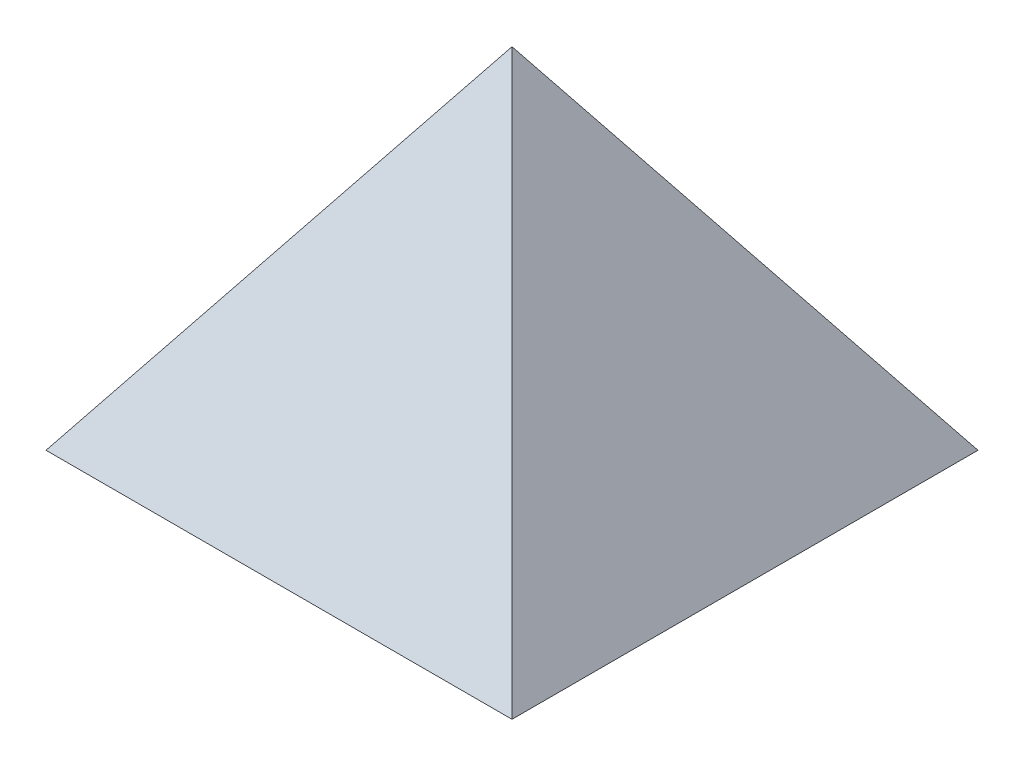
SolidWorks part; units mm, degrees
ref_plane "Front Plane" through (0, 0, 0) normal (0, 0, 1) x (1, 0, 0)
ref_plane "Top Plane" through (0, 0, 0) normal (0, 1, 0) x (1, 0, 0)
ref_plane "Right Plane" through (0, 0, 0) normal (1, 0, 0) x (0, 0, -1)
sketch "Sketch3" plane through (0, 0, 0) normal (0, 1, 0) x (1, 0, 0)
  line L1 (-50.8, -50.8) -> (50.8, -50.8)
  line L2 (-50.8, -50.8) -> (-50.8, 50.8)
  line L3 (-50.8, 50.8) -> (50.8, 50.8)
  line L4 (50.8, -50.8) -> (50.8, 50.8)
  line L5 (-50.8, -50.8) -> (50.8, 50.8) construction
  line L6 (-50.8, 50.8) -> (50.8, -50.8) construction
  point P0 (0, 0)
  dimension "D1" = 101.6
  dimension "D2" = 101.6
ref_plane "Plane4" through (0, 76.2, 0) normal (0, 1, 0) x (1, 0, 0)
sketch "Sketch4" plane through (0, 76.2, 0) normal (0, 1, 0) x (1, 0, 0)
  point P0 (0, 0)
loft "Loft1" add profiles "Sketch4", "Sketch3"
sketch "Sketch7" plane through (0, 23.4462, -35.1692) normal (0, 0.5547, -0.8321) x (-1, 0, 0)
  line L0 (-31.3891, -16.7488) -> (31.3891, -16.7488) construction
  line L1 (31.3891, -16.7488) -> (0, 39.8387) construction
  line L2 (0, 39.8387) -> (-31.3891, -16.7488) construction
  line L3 (0, 63.4022) -> (-50.8, -28.1788) construction
  line L4 (0, 63.4022) -> (50.8, -28.1788) construction
  line L5 (-50.8, -28.1788) -> (50.8, -28.1788) construction
  text T0 "R" font "Century Gothic" height in points 60
  text T1 "9" font "Century Gothic" height in points 60
  text T2 "&" font "Century Gothic" height in points 60
  text T3 "#" font "Century Gothic" height in points 60
  point P21 (0, 0)
  dimension "D1" = 11.43
  dimension "D2" = 11.43
  dimension "D3" = 11.43
  dimension "D4" = 22.86
  dimension "D5" = 6.35
  dimension "D6" = 0
  dimension "D7" = 17.78
  dimension "D8" = 0
  dimension "D9" = 4.318
  dimension "D10" = 3.81
  dimension "D11" = 7.62
shell "Shell2" thickness 2.54 removed face at (0, 0, 0)
sketch "Sketch8" plane through (0, 0, 0) normal (0, -1, 0) x (1, 0, 0)
  line L1 (47.7473, -47.7473) -> (-47.7473, -47.7473)
  line L2 (47.7473, -47.7473) -> (47.7473, 47.7473)
  line L3 (47.7473, 47.7473) -> (-47.7473, 47.7473)
  line L4 (-47.7473, -47.7473) -> (-47.7473, 47.7473)
extrude "Boss-Extrude1" add sketch "Sketch8" against normal blind 2.54
sketch "Sketch9" plane through (0, 23.4462, -35.1692) normal (0, 0.5547, -0.8321) x (-1, 0, 0)
  line L0 (-50.8, -28.1788) -> (50.8, -28.1788) construction
  circle A0 centre (35.4584, -19.2888) radius 5.715
  dimension "D1" = 11.43
  dimension "D2" = 8.89
  dimension "D3" = 15.3416
extrude "Cut-Extrude1" cut sketch "Sketch9" against normal blind 2.54
extrude "Boss-Extrude2" [suppressed] add sketch "Sketch7" along normal blind 2.54 and the other way blind 2.54
sketch "Sketch10" plane through (0, 23.4462, -35.1692) normal (0, 0.5547, -0.8321) x (-1, 0, 0)
  line L3 (0, 63.4022) -> (-50.8, -28.1788)
  line L4 (-50.8, -28.1788) -> (50.8, -28.1788)
  line L5 (50.8, -28.1788) -> (0, 63.4022)
  line L6 (0, 63.4022) -> (-50.8, -28.1788)
  line L7 (-50.8, -28.1788) -> (50.8, -28.1788)
  line L8 (50.8, -28.1788) -> (0, 63.4022)
  dimension "D1" = 0
extrude "Cut-Extrude2" [suppressed] cut sketch "Sketch10" against normal through all draft 20 draft outward yes
sketch "Sketch15" plane through (-35.1692, 23.4462, 0) normal (-0.8321, 0.5547, 0) x (0, 0, 1)
  line L0 (-31.3891, -16.7488) -> (31.3891, -16.7488) construction
  line L1 (31.3891, -16.7488) -> (0, 39.8387) construction
  line L2 (0, 39.8387) -> (-31.3891, -16.7488) construction
  line L4 (-50.8, -28.1788) -> (50.8, -28.1788) construction
  line L5 (0, 63.4022) -> (50.8, -28.1788) construction
  line L6 (0, 63.4022) -> (-50.8, -28.1788) construction
  text T0 "O" font "Century Gothic" height in points 60
  text T1 "#" font "Century Gothic" height in points 60
  text T2 "9" font "Century Gothic" height in points 60
  text T3 "&" font "Century Gothic" height in points 60
  point P14 (0, 0)
  dimension "D1" = 11.43
  dimension "D2" = 11.43
  dimension "D3" = 11.43
  dimension "D4" = 21.59
  dimension "D5" = 8.382
  dimension "D6" = 23.622
  dimension "D7" = 0
  dimension "D8" = 4.064
  dimension "D9" = 6.096
  dimension "D10" = 3.048
extrude "Boss-Extrude3" [suppressed] add sketch "Sketch15" along normal blind 2.54 and the other way blind 2.54
sketch "Sketch16" plane through (0, 23.4462, 35.1692) normal (0, 0.5547, 0.8321) x (1, 0, 0)
  line L6 (0, 39.8387) -> (-31.3891, -16.7488)
  line L7 (-31.3891, -16.7488) -> (31.3891, -16.7488)
  line L8 (31.3891, -16.7488) -> (0, 39.8387)
  line L9 (0, 39.8387) -> (-31.3891, -16.7488) construction
  line L10 (-31.3891, -16.7488) -> (31.3891, -16.7488) construction
  line L11 (31.3891, -16.7488) -> (0, 39.8387) construction
  text T0 "S" font "Century Gothic" height in points 60
  text T1 "&" font "Century Gothic" height in points 60
  text T2 "#" font "Century Gothic" height in points 60
  text T3 "9" font "Century Gothic" height in points 60
  dimension "D1" = 11.43
extrude "Boss-Extrude4" [suppressed] add sketch "Sketch16" along normal blind 2.54 and the other way blind 2.54
sketch "Sketch17" plane through (35.1692, 23.4462, 0) normal (0.8321, 0.5547, 0) x (0, 0, -1)
  line L6 (0, 39.8387) -> (-31.3891, -16.7488)
  line L7 (-31.3891, -16.7488) -> (31.3891, -16.7488)
  line L8 (31.3891, -16.7488) -> (0, 39.8387)
  line L9 (0, 39.8387) -> (-31.3891, -16.7488) construction
  line L10 (-31.3891, -16.7488) -> (31.3891, -16.7488) construction
  line L11 (31.3891, -16.7488) -> (0, 39.8387) construction
  text T0 "E" font "Century Gothic" height in points 60
  text T1 "&" font "Century Gothic" height in points 60
  text T2 "#" font "Century Gothic" height in points 60
  text T3 "9" font "Century Gothic" height in points 60
  dimension "D1" = 11.43
extrude "Boss-Extrude5" [suppressed] add sketch "Sketch17" along normal blind 2.54 and the other way blind 2.54
sketch "Sketch20" [suppressed] plane through (0, 23.4462, -35.1692) normal (0, 0.5547, -0.8321) x (-1, 0, 0)
  line L0 (-15.1966, -12.4684) -> (-16.7867, -10.8465) construction
  line L1 (-16.7867, -10.8465) -> (-19.1781, -8.3343) construction
  line L2 (-15.292, -14.3192) -> (-12.907, -16.7488) construction
  line L3 (-12.907, -16.7488) -> (-10.9925, -16.7488) construction
  line L4 (-12.3027, -11.8896) -> (-13.2027, -10.8465) construction
  line L5 (17.6796, -17.1558) -> (22.5674, -10.007) construction
  line L6 (20.9551, -9.9116) -> (16.5411, -16.364) construction
  line L7 (16.5411, -16.364) -> (17.6796, -17.1558) construction
  line L8 (5.8127, 2.7028) -> (2.9315, 2.7028) construction
  line L9 (2.9315, 2.7028) -> (3.4785, 6.3663) construction
  line L10 (3.4785, 6.3663) -> (6.2197, 6.3663) construction
  line L11 (6.2197, 6.3663) -> (6.2197, 7.3839) construction
  line L12 (6.2197, 7.3839) -> (3.6312, 7.3839) construction
  line L13 (3.6312, 7.3839) -> (4.3944, 12.4721) construction
  line L14 (4.3944, 12.4721) -> (3.1669, 12.4721) construction
  line L15 (3.1669, 12.4721) -> (2.4036, 7.3839) construction
  line L16 (2.4036, 7.3839) -> (-0.8464, 7.3839) construction
  line L17 (-0.8464, 7.3839) -> (-0.0832, 12.4721) construction
  line L18 (-0.0832, 12.4721) -> (-1.3107, 12.4721) construction
  line L19 (-1.3107, 12.4721) -> (-2.0739, 7.3839) construction
  line L20 (-2.0739, 7.3839) -> (-5.1777, 7.3839) construction
  line L21 (-5.1777, 7.3839) -> (-5.1777, 6.3663) construction
  line L22 (-5.1777, 6.3663) -> (-2.2266, 6.3663) construction
  line L23 (-2.2266, 6.3663) -> (-2.7767, 2.7028) construction
  line L24 (-2.7767, 2.7028) -> (-5.5847, 2.7028) construction
  line L25 (-5.5847, 2.7028) -> (-5.5847, 1.6852) construction
  line L26 (-5.5847, 1.6852) -> (-2.9294, 1.6852) construction
  line L27 (-2.9294, 1.6852) -> (-3.753, -3.81) construction
  line L28 (-3.753, -3.81) -> (-2.5223, -3.81) construction
  line L29 (-2.5223, -3.81) -> (-1.6987, 1.6852) construction
  line L30 (-1.6987, 1.6852) -> (1.5482, 1.6852) construction
  line L31 (1.5482, 1.6852) -> (0.7246, -3.81) construction
  line L32 (0.7246, -3.81) -> (1.9552, -3.81) construction
  line L33 (1.9552, -3.81) -> (2.7789, 1.6852) construction
  line L34 (2.7789, 1.6852) -> (5.8127, 1.6852) construction
  line L35 (5.8127, 1.6852) -> (5.8127, 2.7028) construction
  line L36 (-4.3147, 32.8537) -> (-4.3147, 16.9787) construction
  line L37 (-4.3147, 16.9787) -> (-2.8901, 16.9787) construction
  line L38 (-2.8901, 16.9787) -> (-2.8901, 24.3056) construction
  line L39 (-2.8901, 24.3056) -> (-1.7325, 24.3056) construction
  line L40 (-1.7325, 24.3056) -> (4.0998, 16.9787) construction
  line L41 (4.0998, 16.9787) -> (5.8615, 16.9787) construction
  line L42 (5.8615, 16.9787) -> (0.0293, 24.3056) construction
  line L43 (-1.1378, 32.8537) -> (-4.3147, 32.8537) construction
  line L44 (-15.1966, -12.4684) -> (-16.7867, -10.8465)
  line L45 (-16.7867, -10.8465) -> (-19.1781, -8.3343)
  line L46 (-15.292, -14.3192) -> (-12.907, -16.7488)
  line L47 (-12.907, -16.7488) -> (-10.9925, -16.7488)
  line L48 (-12.3027, -11.8896) -> (-13.2027, -10.8465)
  line L49 (17.6796, -17.1558) -> (22.5674, -10.007)
  line L50 (20.9551, -9.9116) -> (16.5411, -16.364)
  line L51 (16.5411, -16.364) -> (17.6796, -17.1558)
  line L52 (5.8127, 2.7028) -> (2.9315, 2.7028)
  line L53 (2.9315, 2.7028) -> (3.4785, 6.3663)
  line L54 (3.4785, 6.3663) -> (6.2197, 6.3663)
  line L55 (6.2197, 6.3663) -> (6.2197, 7.3839)
  line L56 (6.2197, 7.3839) -> (3.6312, 7.3839)
  line L57 (3.6312, 7.3839) -> (4.3944, 12.4721)
  line L58 (4.3944, 12.4721) -> (3.1669, 12.4721)
  line L59 (3.1669, 12.4721) -> (2.4036, 7.3839)
  line L60 (2.4036, 7.3839) -> (-0.8464, 7.3839)
  line L61 (-0.8464, 7.3839) -> (-0.0832, 12.4721)
  line L62 (-0.0832, 12.4721) -> (-1.3107, 12.4721)
  line L63 (-1.3107, 12.4721) -> (-2.0739, 7.3839)
  line L64 (-2.0739, 7.3839) -> (-5.1777, 7.3839)
  line L65 (-5.1777, 7.3839) -> (-5.1777, 6.3663)
  line L66 (-5.1777, 6.3663) -> (-2.2266, 6.3663)
  line L67 (-2.2266, 6.3663) -> (-2.7767, 2.7028)
  line L68 (-2.7767, 2.7028) -> (-5.5847, 2.7028)
  line L69 (-5.5847, 2.7028) -> (-5.5847, 1.6852)
  line L70 (-5.5847, 1.6852) -> (-2.9294, 1.6852)
  line L71 (-2.9294, 1.6852) -> (-3.753, -3.81)
  line L72 (-3.753, -3.81) -> (-2.5223, -3.81)
  line L73 (-2.5223, -3.81) -> (-1.6987, 1.6852)
  line L74 (-1.6987, 1.6852) -> (1.5482, 1.6852)
  line L75 (1.5482, 1.6852) -> (0.7246, -3.81)
  line L76 (0.7246, -3.81) -> (1.9552, -3.81)
  line L77 (1.9552, -3.81) -> (2.7789, 1.6852)
  line L78 (2.7789, 1.6852) -> (5.8127, 1.6852)
  line L79 (5.8127, 1.6852) -> (5.8127, 2.7028)
  line L80 (-4.3147, 32.8537) -> (-4.3147, 16.9787)
  line L81 (-4.3147, 16.9787) -> (-2.8901, 16.9787)
  line L82 (-2.8901, 16.9787) -> (-2.8901, 24.3056)
  line L83 (-2.8901, 24.3056) -> (-1.7325, 24.3056)
  line L84 (-1.7325, 24.3056) -> (4.0998, 16.9787)
  line L85 (4.0998, 16.9787) -> (5.8615, 16.9787)
  line L86 (5.8615, 16.9787) -> (0.0293, 24.3056)
  line L87 (-1.1378, 32.8537) -> (-4.3147, 32.8537)
  line L88 (-16.262, -13.3334) -> (-18.8092, -10.7352) construction
  line L89 (-1.546, 2.7028) -> (1.7008, 2.7028) construction
  line L90 (1.7008, 2.7028) -> (2.251, 6.3663) construction
  line L91 (2.251, 6.3663) -> (-0.9991, 6.3663) construction
  line L92 (-0.9991, 6.3663) -> (-1.546, 2.7028) construction
  line L93 (0.0865, 31.2255) -> (-2.8901, 31.2255) construction
  line L94 (-2.8901, 31.2255) -> (-2.8901, 25.9338) construction
  line L95 (-2.8901, 25.9338) -> (0.0165, 25.9116) construction
  line L96 (-16.262, -13.3334) -> (-18.8092, -10.7352)
  line L97 (-1.546, 2.7028) -> (1.7008, 2.7028)
  line L98 (1.7008, 2.7028) -> (2.251, 6.3663)
  line L99 (2.251, 6.3663) -> (-0.9991, 6.3663)
  line L100 (-0.9991, 6.3663) -> (-1.546, 2.7028)
  line L101 (0.0865, 31.2255) -> (-2.8901, 31.2255)
  line L102 (-2.8901, 31.2255) -> (-2.8901, 25.9338)
  line L103 (-2.8901, 25.9338) -> (0.0165, 25.9116)
  spline S0 degree 3 poles (-1211.016, 1589.987) (37.766, 13.4921) (7.6344, 6.2742) (-14.1134, -11.5897) (-53.1946, -43.2278) (-85.728, -82.5813) (-1389.1326, 1438.1841) knots -32.138305 -32.138305 -32.138305 -32.138305 0.211979 0.448506 0.7115 58.901746 58.901746 58.901746 58.901746 only from (-13.2027, -10.8465) to (-15.1966, -12.4684) construction
  spline S1 degree 3 poles (1213.8222, -1582.7079) (-59.2714, -14.9852) (-32.1987, -19.4765) (-18.3945, -7.68) (-18.0524, -7.3699) (-17.7457, -7.0763) (-17.4726, -6.7989) (-17.2383, -6.5365) (-17.0382, -6.2896) (-16.823, -5.988) (-16.6097, -5.6247) (-16.4256, -5.1931) (-14.3902, 1.855) (-54.3612, 14.9464) (1965.0086, -276.0147) knots -10.451764 -10.451764 -10.451764 -10.451764 0.105642 0.203981 0.294597 0.378912 0.455227 0.524996 0.587023 0.643258 0.744199 0.835566 0.920643 5.054796 5.054796 5.054796 5.054796 only from (-19.1781, -8.3343) to (-16.2842, -4.3623) construction
  spline S2 degree 3 poles (1973.7793, 194.0657) (-51.4849, -21.917) (-14.7602, -10.7247) (-16.381, -3.6302) (-16.5173, -3.2786) (-16.7047, -2.9408) (-16.9387, -2.6211) (-17.2268, -2.3363) (-17.559, -2.0826) (-17.9391, -1.8731) (-18.3484, -1.6979) (-18.7863, -1.5731) (-28.3709, -0.0333) (-40.7081, -35.3731) (109.6458, 1994.1865) knots -4.132886 -4.132886 -4.132886 -4.132886 0.074197 0.148047 0.222587 0.300557 0.37994 0.460256 0.543595 0.630739 0.720813 0.811094 0.904147 6.547345 6.547345 6.547345 6.547345 only from (-16.2842, -4.3623) to (-19.7187, -1.4843) construction
  spline S3 degree 3 poles (-96.2047, 1996.9105) (-1.1162, -30.4751) (-11.5215, -0.5018) (-20.4569, -1.5327) (-20.8041, -1.6037) (-21.1379, -1.6965) (-21.4523, -1.828) (-21.7571, -1.974) (-28.7123, -6.4707) (-17.3542, -34.8268) (-1252.8823, 1574.128) knots -9.254206 -9.254206 -9.254206 -9.254206 0.135626 0.266321 0.392983 0.516276 0.637901 0.758631 0.879017 9.511566 9.511566 9.511566 9.511566 only from (-19.7187, -1.4843) to (-22.3041, -2.3684) construction
  spline S4 degree 3 poles (-1373.4615, 1472.0964) (6.456, -12.0068) (-17.6213, 2.8205) (-22.7023, -2.7663) (-22.8532, -2.9916) (-22.984, -3.225) (-23.0817, -3.4736) (-23.1511, -3.734) (-24.2565, -10.0188) (7.5119, -18.9958) (-2017.4492, 146.1379) knots -9.92722 -9.92722 -9.92722 -9.92722 0.131449 0.257906 0.381113 0.501946 0.623787 0.745627 0.870676 9.333997 9.333997 9.333997 9.333997 only from (-22.3041, -2.3684) to (-23.2041, -4.286) construction
  spline S5 degree 3 poles (-2015.3815, -179.3604) (8.1381, 12.7979) (-24.523, 2.2958) (-23.123, -4.9748) (-23.0129, -5.329) (-22.8872, -5.632) (-22.7505, -5.8874) (-22.6249, -6.1097) (-22.4672, -6.3547) (-22.2813, -6.6244) (-22.0732, -6.9226) (-21.8364, -7.2447) (-11.1832, -21.2383) (14.4163, -23.4182) (-1566.5908, -1277.2192) knots -4.999634 -4.999634 -4.999634 -4.999634 0.080148 0.163016 0.250603 0.343925 0.395896 0.456723 0.525583 0.60322 0.689875 0.784341 0.887706 13.206881 13.206881 13.206881 13.206881 only from (-23.2041, -4.286) to (-21.2865, -7.9526) construction
  spline S6 degree 3 poles (-1258.508, 1562.9871) (24.2351, -1.632) (-7.0336, 4.4872) (-22.3165, -8.8237) (-22.7641, -9.2371) (-23.1684, -9.6273) (-23.5183, -10.0028) (-23.829, -10.351) (-24.0821, -10.6865) (-24.3605, -11.0941) (-24.6251, -11.6) (-24.8626, -12.2056) (-27.2311, -22.2702) (15.6235, -37.4436) (-2014.3666, 191.7077) knots -8.568615 -8.568615 -8.568615 -8.568615 0.10298 0.198866 0.287721 0.369301 0.444358 0.512001 0.573159 0.6279 0.727593 0.821895 0.911698 5.220728 5.220728 5.220728 5.220728 only from (-21.2865, -7.9526) to (-25.0358, -13.4256) construction
  spline S7 degree 3 poles (-2021.6065, -128.263) (6.2867, 5.1239) (-26.1824, -5.6484) (-24.9748, -14.1887) (-24.8934, -14.5482) (-24.7742, -14.8912) (-24.6218, -15.2182) (-24.4366, -15.5285) (-24.217, -15.8206) (-23.9682, -16.0957) (-23.6901, -16.345) (-23.3888, -16.5651) (-23.0626, -16.7449) (-22.7168, -16.8957) (-22.3495, -17.0143) (-21.9592, -17.095) (-12.5827, -18.3074) (-1.1632, 14.4463) (-121.9288, -2014.4951) knots -4.067076 -4.067076 -4.067076 -4.067076 0.064496 0.126884 0.187124 0.246441 0.305977 0.36519 0.424708 0.486277 0.548235 0.609019 0.670238 0.731947 0.79524 0.860594 0.928698 5.460162 5.460162 5.460162 5.460162 only from (-25.0358, -13.4256) to (-21.1211, -17.1558) construction
  spline S8 degree 3 poles (105.4375, -2012.9623) (-46.4777, 21.2594) (-31.562, -18.9943) (-19.8205, -17.028) (-19.1948, -16.8473) (-18.6812, -16.6419) (-18.2652, -16.4305) (-17.923, -16.2343) (-17.554, -16.0024) (-17.1543, -15.7376) (-16.7283, -15.4348) (-16.2759, -15.0935) (-0.8159, -3.2749) (-0.512, 27.4826) (1265.8678, -1549.7318) knots -5.076743 -5.076743 -5.076743 -5.076743 0.099479 0.19723 0.295054 0.393883 0.447109 0.506216 0.572397 0.644405 0.723232 0.808942 0.900994 9.532577 9.532577 9.532577 9.532577 only from (-21.1211, -17.1558) to (-15.292, -14.3192) construction
  spline S9 degree 3 poles (1466.2951, 1330.8092) (10.7971, -58.9757) (4.6752, -32.6363) (-11.6795, -16.046) (-46.1587, 19.0578) (-86.0822, 48.5893) (1308.3834, 1484.0297) knots -33.089565 -33.089565 -33.089565 -33.089565 0.227433 0.471173 0.72797 71.654968 71.654968 71.654968 71.654968 only from (-10.9925, -16.7488) to (-12.4395, -15.2732) construction
  spline S10 degree 3 poles (1478.6723, 1316.367) (21.6085, -71.1392) (9.5912, -37.4776) (-13.3896, -14.3089) (-33.2104, 6.0641) (-62.8373, 16.5022) (1352.8811, 1445.4489) knots -37.612235 -37.612235 -37.612235 -37.612235 0.277779 0.537034 0.77778 33.71632 33.71632 33.71632 33.71632 only from (-12.4395, -15.2732) to (-14.2267, -13.4542) construction
  spline S11 degree 3 poles (-1341.9172, 1481.3358) (-50.1448, -60.2796) (-36.1748, -31.1825) (-13.2966, -12.6979) (27.3008, 20.3634) (73.138, 46.6573) (-1148.1149, 1631.7199) knots -34.846163 -34.846163 -34.846163 -34.846163 0.235134 0.479473 0.735631 63.573763 63.573763 63.573763 63.573763 only from (-14.2267, -13.4542) to (-12.3027, -11.8896) construction
  spline S12 degree 3 poles (1668.2044, -1146.2833) (-10.7043, -24.0989) (14.6997, -22.3807) (23.0413, -9.2835) (23.2502, -8.9385) (23.4351, -8.6061) (23.6071, -8.2897) (23.7545, -7.9854) (23.8874, -7.6962) (24.0286, -7.3301) (24.1749, -6.8869) (24.3038, -6.3632) (25.8363, 4.0048) (-8.4285, 16.8712) (2020.7141, -124.8402) knots -8.910329 -8.910329 -8.910329 -8.910329 0.087946 0.171747 0.250583 0.32591 0.396143 0.462994 0.525418 0.583838 0.694397 0.800583 0.90168 6.863836 6.863836 6.863836 6.863836 only from (22.5674, -10.007) to (24.3959, -5.345) construction
  spline S13 degree 3 poles (2017.2359, 161.6488) (-15.7997, -30.0858) (26.4308, -14.9769) (24.2462, -4.0769) (24.0418, -3.4701) (23.7584, -2.8888) (23.4055, -2.3477) (22.9865, -1.8624) (22.5022, -1.4445) (21.9636, -1.0938) (21.3819, -0.814) (20.7699, -0.6115) (9.3934, 1.527) (-5.7744, -39.9197) (169.9675, 1993.6962) knots -4.058346 -4.058346 -4.058346 -4.058346 0.083474 0.165402 0.248081 0.332 0.416297 0.498735 0.580591 0.664318 0.748057 0.830997 0.914468 5.233291 5.233291 5.233291 5.233291 only from (24.3959, -5.345) to (19.4763, -0.4667) construction
  spline S14 degree 3 poles (-127.7649, 1993.9185) (44.9609, -40.2134) (29.6793, 1.5495) (18.1496, -0.6145) (17.5161, -0.8243) (16.9113, -1.1088) (16.3516, -1.4626) (15.8504, -1.8742) (15.419, -2.3441) (15.0601, -2.8658) (14.7751, -3.4318) (14.5708, -4.034) (12.3869, -15.2278) (54.9701, -30.4623) (-1979.29, 151.7815) knots -4.230904 -4.230904 -4.230904 -4.230904 0.086062 0.17094 0.255778 0.341735 0.427007 0.509416 0.590092 0.671171 0.751825 0.832673 0.914751 5.113135 5.113135 5.113135 5.113135 only from (19.4763, -0.4667) to (14.4232, -5.3291) construction
  spline S15 degree 3 poles (-1982.2681, -117.5572) (47.9002, 15.9969) (13.054, 3.6541) (14.5041, -6.2813) (14.6155, -6.7306) (14.7685, -7.1623) (14.9702, -7.5716) (15.213, -7.9642) (15.5053, -8.3323) (15.8332, -8.6801) (16.1939, -8.9969) (16.5785, -9.2736) (16.9829, -9.5088) (17.4066, -9.6985) (17.8487, -9.8511) (18.3108, -9.9534) (28.6348, -11.379) (41.3764, 22.9838) (-94.5785, -2006.6302) knots -3.797348 -3.797348 -3.797348 -3.797348 0.064609 0.12725 0.188534 0.248578 0.309139 0.369772 0.431966 0.495825 0.559795 0.622662 0.68409 0.74564 0.807138 0.869869 0.933705 4.947275 4.947275 4.947275 4.947275 only from (14.4232, -5.3291) to (19.2855, -10.0324) construction
  spline S16 degree 3 poles (119.0292, -2007.3224) (-12.2834, 26.9885) (23.1112, -49.516) (47.1443, 32.0919) (208.2591, -2000.898) knots -26.084625 -26.084625 -26.084625 -26.084625 0.492142 27.359519 27.359519 27.359519 27.359519 only from (19.2855, -10.0324) to (20.9551, -9.9116) construction
  spline S17 degree 3 poles (13.5867, -1975.4638) (-27.7179, 48.4127) (-13.0892, 23.5705) (0.9903, 24.337) (1.4338, 24.3781) (1.85, 24.4341) (2.2379, 24.5083) (2.5993, 24.5911) (2.9306, 24.6983) (3.3329, 24.8507) (3.7885, 25.0886) (4.2778, 25.4317) (4.6965, 25.8417) (5.045, 26.3085) (5.3186, 26.8263) (5.5171, 27.385) (7.6544, 37.9462) (-35.3403, 52.6149) (1999.1094, -131.0337) knots -5.078847 -5.078847 -5.078847 -5.078847 0.062052 0.120621 0.175789 0.228041 0.2771 0.323011 0.366127 0.406783 0.483311 0.556994 0.62881 0.700809 0.773286 0.846279 0.92122 4.77063 4.77063 4.77063 4.77063 only from (0.0293, 24.3056) to (5.658, 28.6083) construction
  spline S18 degree 3 poles (2003.9003, 109.732) (-23.2225, 9.7328) (6.6402, 20.3137) (5.6096, 29.3548) (5.5396, 29.7081) (5.4404, 30.0449) (5.3172, 30.3683) (5.1624, 30.6752) (4.9828, 30.9687) (4.7699, 31.2401) (4.5441, 31.4988) (4.2939, 31.7306) (4.0294, 31.9414) (3.7494, 32.1299) (3.451, 32.2931) (3.1357, 32.4319) (-4.8385, 35.3242) (-21.5091, 8.2328) (543.2062, 1958.0336) knots -4.680958 -4.680958 -4.680958 -4.680958 0.068359 0.134815 0.198683 0.261561 0.323202 0.38431 0.445928 0.507648 0.56935 0.630173 0.690547 0.750868 0.811255 0.872936 0.935783 5.359963 5.359963 5.359963 5.359963 only from (5.658, 28.6083) to (2.4588, 32.6374) construction
  spline S19 degree 3 poles (378.3496, 1996.9387) (13.9488, 7.4413) (10.0374, 31.6395) (1.8639, 32.7373) (1.4934, 32.7698) (1.0706, 32.8038) (0.5943, 32.8224) (0.0644, 32.8441) (-26.6805, 33.1906) (-53.1799, 16.841) (-87.9157, 2030.4344) knots -6.585191 -6.585191 -6.585191 -6.585191 0.073628 0.162615 0.265302 0.382842 0.515178 0.661566 0.823742 22.749636 22.749636 22.749636 22.749636 only from (2.4588, 32.6374) to (-1.1378, 32.8537) construction
  spline S20 degree 3 poles (-13.2027, -10.8465) (-13.3438, -10.9609) (-13.6424, -11.2028) (-14.1134, -11.5897) (-14.6381, -12.0145) (-15.0048, -12.3125) (-15.1966, -12.4684) knots 0 0 0 0 0.211979 0.448506 0.7115 1 1 1 1
  spline S21 degree 3 poles (-19.1781, -8.3343) (-19.0399, -8.2214) (-18.7729, -8.0034) (-18.3945, -7.68) (-18.0524, -7.3699) (-17.7457, -7.0763) (-17.4726, -6.7989) (-17.2383, -6.5365) (-17.0382, -6.2896) (-16.823, -5.988) (-16.6097, -5.6247) (-16.4256, -5.1931) (-16.3048, -4.7749) (-16.2909, -4.4966) (-16.2842, -4.3623) knots 0 0 0 0 0.105642 0.203981 0.294597 0.378912 0.455227 0.524996 0.587023 0.643258 0.744199 0.835566 0.920643 1 1 1 1
  spline S22 degree 3 poles (-16.2842, -4.3623) (-16.2889, -4.2389) (-16.2981, -3.9927) (-16.381, -3.6302) (-16.5173, -3.2786) (-16.7047, -2.9408) (-16.9387, -2.6211) (-17.2268, -2.3363) (-17.559, -2.0826) (-17.9391, -1.8731) (-18.3484, -1.6979) (-18.7863, -1.5731) (-19.2455, -1.4993) (-19.5594, -1.4894) (-19.7187, -1.4843) knots 0 0 0 0 0.074197 0.148047 0.222587 0.300557 0.37994 0.460256 0.543595 0.630739 0.720813 0.811094 0.904147 1 1 1 1
  spline S23 degree 3 poles (-19.7187, -1.4843) (-19.845, -1.4865) (-20.0929, -1.4907) (-20.4569, -1.5327) (-20.8041, -1.6037) (-21.1379, -1.6965) (-21.4523, -1.828) (-21.7571, -1.974) (-22.0409, -2.1575) (-22.2162, -2.298) (-22.3041, -2.3684) knots 0 0 0 0 0.135626 0.266321 0.392983 0.516276 0.637901 0.758631 0.879017 1 1 1 1
  spline S24 degree 3 poles (-22.3041, -2.3684) (-22.3751, -2.433) (-22.5145, -2.5597) (-22.7023, -2.7663) (-22.8532, -2.9916) (-22.984, -3.225) (-23.0817, -3.4736) (-23.1511, -3.734) (-23.1989, -4.0055) (-23.2023, -4.1915) (-23.2041, -4.286) knots 0 0 0 0 0.131449 0.257906 0.381113 0.501946 0.623787 0.745627 0.870676 1 1 1 1
  spline S25 degree 3 poles (-23.2041, -4.286) (-23.1994, -4.3986) (-23.1899, -4.6277) (-23.123, -4.9748) (-23.0129, -5.329) (-22.8872, -5.632) (-22.7505, -5.8874) (-22.6249, -6.1097) (-22.4672, -6.3547) (-22.2813, -6.6244) (-22.0732, -6.9226) (-21.8364, -7.2447) (-21.5725, -7.5914) (-21.3844, -7.8289) (-21.2865, -7.9526) knots 0 0 0 0 0.080148 0.163016 0.250603 0.343925 0.395896 0.456723 0.525583 0.60322 0.689875 0.784341 0.887706 1 1 1 1
  spline S26 degree 3 poles (-21.2865, -7.9526) (-21.4685, -8.1023) (-21.82, -8.3912) (-22.3165, -8.8237) (-22.7641, -9.2371) (-23.1684, -9.6273) (-23.5183, -10.0028) (-23.829, -10.351) (-24.0821, -10.6865) (-24.3605, -11.0941) (-24.6251, -11.6) (-24.8626, -12.2056) (-25.0062, -12.8158) (-25.026, -13.2235) (-25.0358, -13.4256) knots 0 0 0 0 0.10298 0.198866 0.287721 0.369301 0.444358 0.512001 0.573159 0.6279 0.727593 0.821895 0.911698 1 1 1 1
  spline S27 degree 3 poles (-25.0358, -13.4256) (-25.0332, -13.5561) (-25.028, -13.813) (-24.9748, -14.1887) (-24.8934, -14.5482) (-24.7742, -14.8912) (-24.6218, -15.2182) (-24.4366, -15.5285) (-24.217, -15.8206) (-23.9682, -16.0957) (-23.6901, -16.345) (-23.3888, -16.5651) (-23.0626, -16.7449) (-22.7168, -16.8957) (-22.3495, -17.0143) (-21.9592, -17.095) (-21.5477, -17.1482) (-21.2655, -17.1532) (-21.1211, -17.1558) knots 0 0 0 0 0.064496 0.126884 0.187124 0.246441 0.305977 0.36519 0.424708 0.486277 0.548235 0.609019 0.670238 0.731947 0.79524 0.860594 0.928698 1 1 1 1
  spline S28 degree 3 poles (-21.1211, -17.1558) (-20.9013, -17.1492) (-20.4655, -17.136) (-19.8205, -17.028) (-19.1948, -16.8473) (-18.6812, -16.6419) (-18.2652, -16.4305) (-17.923, -16.2343) (-17.554, -16.0024) (-17.1543, -15.7376) (-16.7283, -15.4348) (-16.2759, -15.0935) (-15.7901, -14.7222) (-15.462, -14.4567) (-15.292, -14.3192) knots 0 0 0 0 0.099479 0.19723 0.295054 0.393883 0.447109 0.506216 0.572397 0.644405 0.723232 0.808942 0.900994 1 1 1 1
  spline S29 degree 3 poles (-10.9925, -16.7488) (-11.1016, -16.6363) (-11.3274, -16.4032) (-11.6795, -16.046) (-12.0524, -15.6663) (-12.308, -15.4067) (-12.4395, -15.2732) knots 0 0 0 0 0.227433 0.471173 0.72797 1 1 1 1
  spline S30 degree 3 poles (-12.4395, -15.2732) (-12.6047, -15.1045) (-12.924, -14.7783) (-13.3896, -14.3089) (-13.8177, -13.8688) (-14.094, -13.5887) (-14.2267, -13.4542) knots 0 0 0 0 0.277779 0.537034 0.77778 1 1 1 1
  spline S31 degree 3 poles (-14.2267, -13.4542) (-14.0763, -13.3311) (-13.7696, -13.08) (-13.2966, -12.6979) (-12.8064, -12.2986) (-12.4724, -12.0274) (-12.3027, -11.8896) knots 0 0 0 0 0.235134 0.479473 0.735631 1 1 1 1
  spline S32 degree 3 poles (22.5674, -10.007) (22.6506, -9.8833) (22.8131, -9.6418) (23.0413, -9.2835) (23.2502, -8.9385) (23.4351, -8.6061) (23.6071, -8.2897) (23.7545, -7.9854) (23.8874, -7.6962) (24.0286, -7.3301) (24.1749, -6.8869) (24.3038, -6.3632) (24.3797, -5.8497) (24.3906, -5.5116) (24.3959, -5.345) knots 0 0 0 0 0.087946 0.171747 0.250583 0.32591 0.396143 0.462994 0.525418 0.583838 0.694397 0.800583 0.90168 1 1 1 1
  spline S33 degree 3 poles (24.3959, -5.345) (24.3879, -5.1303) (24.3721, -4.7048) (24.2462, -4.0769) (24.0418, -3.4701) (23.7584, -2.8888) (23.4055, -2.3477) (22.9865, -1.8624) (22.5022, -1.4445) (21.9636, -1.0938) (21.3819, -0.814) (20.7699, -0.6115) (20.1308, -0.4914) (19.6963, -0.475) (19.4763, -0.4667) knots 0 0 0 0 0.083474 0.165402 0.248081 0.332 0.416297 0.498735 0.580591 0.664318 0.748057 0.830997 0.914468 1 1 1 1
  spline S34 degree 3 poles (19.4763, -0.4667) (19.2522, -0.4749) (18.8069, -0.4912) (18.1496, -0.6145) (17.5161, -0.8243) (16.9113, -1.1088) (16.3516, -1.4626) (15.8504, -1.8742) (15.419, -2.3441) (15.0601, -2.8658) (14.7751, -3.4318) (14.5708, -4.034) (14.4465, -4.671) (14.431, -5.107) (14.4232, -5.3291) knots 0 0 0 0 0.086062 0.17094 0.255778 0.341735 0.427007 0.509416 0.590092 0.671171 0.751825 0.832673 0.914751 1 1 1 1
  spline S35 degree 3 poles (14.4232, -5.3291) (14.4273, -5.4915) (14.4355, -5.8114) (14.5041, -6.2813) (14.6155, -6.7306) (14.7685, -7.1623) (14.9702, -7.5716) (15.213, -7.9642) (15.5053, -8.3323) (15.8332, -8.6801) (16.1939, -8.9969) (16.5785, -9.2736) (16.9829, -9.5088) (17.4066, -9.6985) (17.8487, -9.8511) (18.3108, -9.9534) (18.7918, -10.0198) (19.1189, -10.0282) (19.2855, -10.0324) knots 0 0 0 0 0.064609 0.12725 0.188534 0.248578 0.309139 0.369772 0.431966 0.495825 0.559795 0.622662 0.68409 0.74564 0.807138 0.869869 0.933705 1 1 1 1
  spline S36 degree 3 poles (19.2855, -10.0324) (19.5604, -10.0263) (20.1189, -10.0138) (20.6734, -9.946) (20.9551, -9.9116) knots 0 0 0 0 0.492142 1 1 1 1
  spline S37 degree 3 poles (0.0293, 24.3056) (0.1957, 24.3076) (0.5193, 24.3114) (0.9903, 24.337) (1.4338, 24.3781) (1.85, 24.4341) (2.2379, 24.5083) (2.5993, 24.5911) (2.9306, 24.6983) (3.3329, 24.8507) (3.7885, 25.0886) (4.2778, 25.4317) (4.6965, 25.8417) (5.045, 26.3085) (5.3186, 26.8263) (5.5171, 27.385) (5.6383, 27.984) (5.6513, 28.3967) (5.658, 28.6083) knots 0 0 0 0 0.062052 0.120621 0.175789 0.228041 0.2771 0.323011 0.366127 0.406783 0.483311 0.556994 0.62881 0.700809 0.773286 0.846279 0.92122 1 1 1 1
  spline S38 degree 3 poles (5.658, 28.6083) (5.6558, 28.7356) (5.6516, 28.9867) (5.6096, 29.3548) (5.5396, 29.7081) (5.4404, 30.0449) (5.3172, 30.3683) (5.1624, 30.6752) (4.9828, 30.9687) (4.7699, 31.2401) (4.5441, 31.4988) (4.2939, 31.7306) (4.0294, 31.9414) (3.7494, 32.1299) (3.451, 32.2931) (3.1357, 32.4319) (2.8048, 32.552) (2.575, 32.6087) (2.4588, 32.6374) knots 0 0 0 0 0.068359 0.134815 0.198683 0.261561 0.323202 0.38431 0.445928 0.507648 0.56935 0.630173 0.690547 0.750868 0.811255 0.872936 0.935783 1 1 1 1
  spline S39 degree 3 poles (2.4588, 32.6374) (2.3721, 32.6553) (2.1805, 32.6948) (1.8639, 32.7373) (1.4934, 32.7698) (1.0706, 32.8038) (0.5943, 32.8224) (0.0644, 32.8441) (-0.5188, 32.8516) (-0.9258, 32.853) (-1.1378, 32.8537) knots 0 0 0 0 0.073628 0.162615 0.265302 0.382842 0.515178 0.661566 0.823742 1 1 1 1
  spline S40 degree 3 poles (-2015.1213, -166.603) (5.1086, 7.8543) (-22.7032, 0.259) (-21.7337, -4.8465) (-19.9237, -9.9588) (7.0147, -3.5059) (-1833.8121, -851.0493) knots -18.296929 -18.296929 -18.296929 -18.296929 0.250262 0.500554 0.748645 20.143093 20.143093 20.143093 20.143093 only from (-21.7794, -4.4418) to (-21.5727, -5.221) construction
  spline S41 degree 3 poles (-1721.2086, -1059.1437) (-8.0589, 31.0996) (-28.0764, 3.847) (-20.9593, -6.1601) (-11.4562, -18.6244) (22.4482, -11.0862) (-1545.6046, -1300.1956) knots -14.608317 -14.608317 -14.608317 -14.608317 0.220523 0.461139 0.719906 19.795338 19.795338 19.795338 19.795338 only from (-21.5727, -5.221) to (-20.1544, -7.1544) construction
  spline S42 degree 3 poles (1132.9345, -1641.0776) (-64.4673, 5.6026) (-30.5953, -15.6337) (-19.0161, -6.3174) (-10.9168, 0.9256) (-31.4993, 35.3366) (1446.7939, -1366.7812) knots -16.257371 -16.257371 -16.257371 -16.257371 0.287445 0.548797 0.785479 12.725931 12.725931 12.725931 12.725931 only from (-20.1544, -7.1544) to (-18.1764, -5.4595) construction
  spline S43 degree 3 poles (1663.9584, -1087.1279) (-55.3385, 1.8871) (-21.1743, -11.2532) (-17.828, -4.9157) (-16.0705, -0.4752) (-52.3145, 11.8176) (1942.4707, -401.2811) knots -17.589215 -17.589215 -17.589215 -17.589215 0.300653 0.566171 0.794353 12.433873 12.433873 12.433873 12.433873 only from (-18.1764, -5.4595) to (-17.7089, -4.41) construction
  spline S44 degree 3 poles (1938.5559, 411.163) (-55.3665, -21.49) (-15.8706, -8.1988) (-17.8428, -3.9039) (-18.0284, -3.6818) (-18.2782, -3.4841) (-18.5825, -3.3162) (-18.9384, -3.1951) (-27.8208, -1.6941) (-39.3954, -37.1612) (106.488, 1992.7711) knots -4.873638 -4.873638 -4.873638 -4.873638 0.095564 0.192533 0.297697 0.416353 0.546125 0.68385 0.834051 10.562888 10.562888 10.562888 10.562888 only from (-17.7089, -4.41) to (-19.7728, -3.1126) construction
  spline S45 degree 3 poles (-160.685, 1991.8027) (-0.9697, -37.7012) (-12.2656, -1.6605) (-20.5738, -3.1985) (-20.9204, -3.3242) (-21.221, -3.4934) (-21.4663, -3.6967) (-21.6462, -3.9257) (-23.6235, -8.317) (16.0339, -21.6842) (-1978.6916, 408.2962) knots -9.053975 -9.053975 -9.053975 -9.053975 0.159521 0.306982 0.443331 0.57416 0.694803 0.800649 0.900947 6.033868 6.033868 6.033868 6.033868 only from (-19.7728, -3.1126) to (-21.7794, -4.4418) construction
  spline S46 degree 3 poles (-1453.9053, -1403.4357) (18.2002, -21.8315) (-7.964, -22.7875) (-19.4967, -9.9895) (-33.2828, 5.2368) (-31.7367, 33.8694) (-1553.5296, -1292.7918) knots -23.383883 -23.383883 -23.383883 -23.383883 0.225658 0.468256 0.725626 28.971497 28.971497 28.971497 28.971497 only from (-18.8092, -10.7352) to (-20.2466, -9.1452) construction
  spline S47 degree 3 poles (-1210.0734, 1598.0642) (22.6682, -5.3038) (-6.5802, 1.9) (-21.1825, -9.8782) (-21.5924, -10.2174) (-21.9535, -10.5416) (-22.2721, -10.8434) (-22.5488, -11.1229) (-22.7772, -11.3861) (-23.0187, -11.7) (-23.2492, -12.0767) (-23.4537, -12.5176) (-25.6157, -19.6013) (14.2342, -33.2387) (-2001.5391, 281.8929) knots -9.796355 -9.796355 -9.796355 -9.796355 0.112416 0.216427 0.311718 0.399092 0.477875 0.548155 0.610915 0.665521 0.761427 0.848075 0.927081 4.720743 4.720743 4.720743 4.720743 only from (-20.2466, -9.1452) to (-23.6111, -13.362) construction
  spline S48 degree 3 poles (-2019.5827, -138.7179) (1.9746, 0.152) (-24.4919, -7.7758) (-23.5684, -13.8165) (-23.5062, -14.0344) (-23.4238, -14.2462) (-23.3144, -14.4507) (-23.1808, -14.6477) (-23.0219, -14.836) (-22.8469, -15.0193) (-22.6521, -15.1872) (-22.4398, -15.3295) (-22.2206, -15.4545) (-21.9903, -15.5585) (-21.7469, -15.6323) (-21.4957, -15.692) (-13.9242, -16.5656) (-5.1833, 8.6354) (-95.1441, -2014.2623) knots -4.464912 -4.464912 -4.464912 -4.464912 0.058197 0.11618 0.173161 0.230409 0.288896 0.349333 0.411228 0.476294 0.542121 0.606588 0.670554 0.734141 0.798462 0.863852 0.930519 6.588195 6.588195 6.588195 6.588195 only from (-23.6111, -13.362) to (-20.9621, -15.7311) construction
  spline S49 degree 3 poles (139.9511, -2009.1853) (-40.238, 18.2917) (-28.5352, -17.1452) (-20.1232, -15.6447) (-11.5128, -13.316) (-15.3983, 23.7392) (674.517, -1891.0422) knots -14.233995 -14.233995 -14.233995 -14.233995 0.246277 0.493763 0.743289 15.887755 15.887755 15.887755 15.887755 only from (-20.9621, -15.7311) to (-19.3085, -15.3623) construction
  spline S50 degree 3 poles (869.1163, -1807.0476) (-47.9897, -0.2002) (-27.123, -19.8092) (-18.6317, -15.0116) (-18.272, -14.8012) (-17.9007, -14.5571) (-17.5126, -14.29) (-17.108, -13.9972) (-2.0071, -2.4097) (0.0217, 25.415) (1268.3043, -1545.8285) knots -7.65083 -7.65083 -7.65083 -7.65083 0.099233 0.205135 0.318994 0.439914 0.568292 0.704211 0.848264 16.12948 16.12948 16.12948 16.12948 only from (-19.3085, -15.3623) to (-16.262, -13.3334) construction
  spline S51 degree 3 poles (-64.202, 1996.0913) (38.2436, -29.2952) (27.723, -1.0974) (18.6954, -2.146) (18.3604, -2.2201) (18.0377, -2.3218) (17.728, -2.453) (17.4315, -2.6118) (17.1499, -2.8013) (16.8861, -3.0163) (16.6407, -3.248) (16.4315, -3.501) (16.2519, -3.7624) (16.1028, -4.0356) (15.9894, -4.3222) (15.9049, -4.6201) (14.7654, -11.9975) (45.4615, -21.5236) (-1980.4542, 114.4903) knots -4.953891 -4.953891 -4.953891 -4.953891 0.068712 0.134812 0.199538 0.263335 0.326747 0.390328 0.454126 0.519203 0.58351 0.645497 0.70529 0.763488 0.821856 0.880004 0.939108 5.048794 5.048794 5.048794 5.048794 only from (19.4032, -2.0949) to (15.8479, -5.2496) construction
  spline S52 degree 3 poles (-1979.5562, -139.8762) (46.7317, 10.7748) (14.7161, 1.2077) (15.9083, -5.8792) (15.9957, -6.1771) (16.1129, -6.4651) (16.2671, -6.7403) (16.4563, -7.0014) (16.6781, -7.2514) (16.9296, -7.4864) (17.2048, -7.7021) (17.4987, -7.8904) (17.8062, -8.0495) (18.1285, -8.1771) (18.4632, -8.2797) (18.8133, -8.3531) (28.2106, -9.4006) (39.0684, 18.641) (-61.7078, -2006.6741) knots -3.802942 -3.802942 -3.802942 -3.802942 0.05954 0.117423 0.17444 0.231734 0.289722 0.3492 0.410516 0.47508 0.540094 0.604444 0.668697 0.73211 0.796739 0.862906 0.930462 6.040623 6.040623 6.040623 6.040623 only from (15.8479, -5.2496) to (19.5495, -8.4042) construction
  spline S53 degree 3 poles (104.4338, -2006.5017) (0.1474, 19.1954) (10.9866, -9.4082) (20.2815, -8.3532) (20.6214, -8.2807) (20.9419, -8.1768) (21.2464, -8.0513) (21.5299, -7.8916) (21.7928, -7.7011) (22.0368, -7.4869) (22.2534, -7.249) (22.4464, -7) (22.6104, -6.7388) (22.7399, -6.4622) (22.8465, -6.1768) (22.92, -5.8781) (23.9697, 2.1189) (-4.182, 11.9121) (2020.0379, -111.8012) knots -5.17092 -5.17092 -5.17092 -5.17092 0.072713 0.141547 0.208363 0.272462 0.33539 0.397711 0.459383 0.522098 0.584315 0.644392 0.703345 0.761509 0.82003 0.878517 0.938265 5.455735 5.455735 5.455735 5.455735 only from (19.5495, -8.4042) to (22.9713, -5.2496) construction
  spline S54 degree 3 poles (2019.3229, 114.3067) (-6.6416, -21.5214) (24.0537, -11.9979) (22.9142, -4.6201) (22.8297, -4.3222) (22.7164, -4.0355) (22.5671, -3.7626) (22.3879, -3.4999) (22.175, -3.2491) (21.9301, -3.0161) (21.6659, -2.8013) (21.3844, -2.6118) (21.0879, -2.453) (20.7782, -2.3219) (20.4546, -2.2196) (20.1173, -2.146) (11.0199, -1.0963) (0.4171, -29.3258) (103.5931, 1996.0584) knots -4.0402 -4.0402 -4.0402 -4.0402 0.06076 0.119735 0.177757 0.235999 0.29407 0.353733 0.415973 0.48014 0.545076 0.608735 0.672178 0.735453 0.799112 0.864284 0.930837 5.981084 5.981084 5.981084 5.981084 only from (22.9713, -5.2496) to (19.4032, -2.0949) construction
  spline S55 degree 3 poles (1993.7212, 232.1316) (-31.6445, 10.7005) (5.8396, 22.1799) (4.1289, 29.3625) (3.9797, 29.712) (3.7787, 30.0393) (3.5337, 30.3365) (3.2465, 30.5907) (2.9249, 30.8004) (2.6243, 30.9345) (2.3557, 31.0167) (2.1224, 31.0745) (1.8588, 31.121) (1.5637, 31.1582) (1.2382, 31.1902) (0.8807, 31.2118) (-12.9522, 31.6679) (-26.9758, 10.6436) (-11.4405, 2031.0373) knots -3.752532 -3.752532 -3.752532 -3.752532 0.068814 0.136365 0.204019 0.273064 0.342913 0.410965 0.479169 0.549308 0.587652 0.630647 0.678879 0.731934 0.791111 0.855283 0.925086 8.256402 8.256402 8.256402 8.256402 only from (4.2333, 28.6114) to (0.0865, 31.2255) construction
  spline S56 degree 3 poles (10.3855, -1973.9562) (-23.2088, 49.6968) (-10.9878, 25.3686) (0.7958, 25.9295) (1.1502, 25.9501) (1.4769, 25.9816) (1.7763, 26.0222) (2.048, 26.0731) (2.2926, 26.1323) (2.5779, 26.2239) (2.8965, 26.3691) (3.2427, 26.5803) (3.5375, 26.8459) (3.7866, 27.1497) (3.9868, 27.4837) (4.1279, 27.8439) (5.8564, 35.1275) (-32.011, 46.9635) (1992.6413, -185.0874) knots -6.028454 -6.028454 -6.028454 -6.028454 0.071668 0.138913 0.201185 0.259124 0.312255 0.360682 0.405086 0.445102 0.518778 0.589462 0.658462 0.727283 0.796322 0.863175 0.930949 4.727907 4.727907 4.727907 4.727907 only from (0.0165, 25.9116) to (4.2333, 28.6114) construction
  spline S57 degree 3 poles (-21.7794, -4.4418) (-21.7769, -4.5098) (-21.7718, -4.6458) (-21.7337, -4.8465) (-21.6655, -5.0392) (-21.6038, -5.1601) (-21.5727, -5.221) knots 0 0 0 0 0.250262 0.500554 0.748645 1 1 1 1
  spline S58 degree 3 poles (-21.5727, -5.221) (-21.4824, -5.3727) (-21.2936, -5.6901) (-20.9593, -6.1601) (-20.5809, -6.6564) (-20.3003, -6.9841) (-20.1544, -7.1544) knots 0 0 0 0 0.220523 0.461139 0.719906 1 1 1 1
  spline S59 degree 3 poles (-20.1544, -7.1544) (-19.9465, -7.0143) (-19.5497, -6.7468) (-19.0161, -6.3174) (-18.5521, -5.9025) (-18.2974, -5.6022) (-18.1764, -5.4595) knots 0 0 0 0 0.287445 0.548797 0.785479 1 1 1 1
  spline S60 degree 3 poles (-18.1764, -5.4595) (-18.1057, -5.3658) (-17.9726, -5.1895) (-17.828, -4.9157) (-17.7267, -4.6597) (-17.7146, -4.4903) (-17.7089, -4.41) knots 0 0 0 0 0.300653 0.566171 0.794353 1 1 1 1
  spline S61 degree 3 poles (-17.7089, -4.41) (-17.7156, -4.3241) (-17.7292, -4.1511) (-17.8428, -3.9039) (-18.0284, -3.6818) (-18.2782, -3.4841) (-18.5825, -3.3162) (-18.9384, -3.1951) (-19.3409, -3.1271) (-19.6241, -3.1176) (-19.7728, -3.1126) knots 0 0 0 0 0.095564 0.192533 0.297697 0.416353 0.546125 0.68385 0.834051 1 1 1 1
  spline S62 degree 3 poles (-19.7728, -3.1126) (-19.9141, -3.1174) (-20.1859, -3.1267) (-20.5738, -3.1985) (-20.9204, -3.3242) (-21.221, -3.4934) (-21.4663, -3.6967) (-21.6462, -3.9257) (-21.7592, -4.1767) (-21.7727, -4.3538) (-21.7794, -4.4418) knots 0 0 0 0 0.159521 0.306982 0.443331 0.57416 0.694803 0.800649 0.900947 1 1 1 1
  spline S63 degree 3 poles (-18.8092, -10.7352) (-18.9199, -10.618) (-19.1496, -10.3747) (-19.4967, -9.9895) (-19.868, -9.5793) (-20.1177, -9.2929) (-20.2466, -9.1452) knots 0 0 0 0 0.225658 0.468256 0.725626 1 1 1 1
  spline S64 degree 3 poles (-20.2466, -9.1452) (-20.4126, -9.2716) (-20.7321, -9.515) (-21.1825, -9.8782) (-21.5924, -10.2174) (-21.9535, -10.5416) (-22.2721, -10.8434) (-22.5488, -11.1229) (-22.7772, -11.3861) (-23.0187, -11.7) (-23.2492, -12.0767) (-23.4537, -12.5176) (-23.5839, -12.9444) (-23.6023, -13.2266) (-23.6111, -13.362) knots 0 0 0 0 0.112416 0.216427 0.311718 0.399092 0.477875 0.548155 0.610915 0.665521 0.761427 0.848075 0.927081 1 1 1 1
  spline S65 degree 3 poles (-23.6111, -13.362) (-23.6084, -13.4384) (-23.6028, -13.591) (-23.5684, -13.8165) (-23.5062, -14.0344) (-23.4238, -14.2462) (-23.3144, -14.4507) (-23.1808, -14.6477) (-23.0219, -14.836) (-22.8469, -15.0193) (-22.6521, -15.1872) (-22.4398, -15.3295) (-22.2206, -15.4545) (-21.9903, -15.5585) (-21.7469, -15.6323) (-21.4957, -15.692) (-21.2321, -15.7224) (-21.0533, -15.7282) (-20.9621, -15.7311) knots 0 0 0 0 0.058197 0.11618 0.173161 0.230409 0.288896 0.349333 0.411228 0.476294 0.542121 0.606588 0.670554 0.734141 0.798462 0.863852 0.930519 1 1 1 1
  spline S66 degree 3 poles (-20.9621, -15.7311) (-20.8219, -15.7272) (-20.5407, -15.7192) (-20.1232, -15.6447) (-19.7083, -15.5325) (-19.443, -15.4195) (-19.3085, -15.3623) knots 0 0 0 0 0.246277 0.493763 0.743289 1 1 1 1
  spline S67 degree 3 poles (-19.3085, -15.3623) (-19.1986, -15.3105) (-18.9716, -15.2037) (-18.6317, -15.0116) (-18.272, -14.8012) (-17.9007, -14.5571) (-17.5126, -14.29) (-17.108, -13.9972) (-16.689, -13.6757) (-16.4068, -13.4494) (-16.262, -13.3334) knots 0 0 0 0 0.099233 0.205135 0.318994 0.439914 0.568292 0.704211 0.848264 1 1 1 1
  spline S68 degree 3 poles (19.4032, -2.0949) (19.2823, -2.0984) (19.045, -2.1054) (18.6954, -2.146) (18.3604, -2.2201) (18.0377, -2.3218) (17.728, -2.453) (17.4315, -2.6118) (17.1499, -2.8013) (16.8861, -3.0163) (16.6407, -3.248) (16.4315, -3.501) (16.2519, -3.7624) (16.1028, -4.0356) (15.9894, -4.3222) (15.9049, -4.6201) (15.8569, -4.9311) (15.8509, -5.1423) (15.8479, -5.2496) knots 0 0 0 0 0.068712 0.134812 0.199538 0.263335 0.326747 0.390328 0.454126 0.519203 0.58351 0.645497 0.70529 0.763488 0.821856 0.880004 0.939108 1 1 1 1
  spline S69 degree 3 poles (15.8479, -5.2496) (15.8506, -5.3568) (15.856, -5.5684) (15.9083, -5.8792) (15.9957, -6.1771) (16.1129, -6.4651) (16.2671, -6.7403) (16.4563, -7.0014) (16.6781, -7.2514) (16.9296, -7.4864) (17.2048, -7.7021) (17.4987, -7.8904) (17.8062, -8.0495) (18.1285, -8.1771) (18.4632, -8.2797) (18.8133, -8.3531) (19.1775, -8.3937) (19.4243, -8.4007) (19.5495, -8.4042) knots 0 0 0 0 0.05954 0.117423 0.17444 0.231734 0.289722 0.3492 0.410516 0.47508 0.540094 0.604444 0.668697 0.73211 0.796739 0.862906 0.930462 1 1 1 1
  spline S70 degree 3 poles (19.5495, -8.4042) (19.6757, -8.4008) (19.9215, -8.3941) (20.2815, -8.3532) (20.6214, -8.2807) (20.9419, -8.1768) (21.2464, -8.0513) (21.5299, -7.8916) (21.7928, -7.7011) (22.0368, -7.4869) (22.2534, -7.249) (22.4464, -7) (22.6104, -6.7388) (22.7399, -6.4622) (22.8465, -6.1768) (22.92, -5.8781) (22.9608, -5.5677) (22.9677, -5.3567) (22.9713, -5.2496) knots 0 0 0 0 0.072713 0.141547 0.208363 0.272462 0.33539 0.397711 0.459383 0.522098 0.584315 0.644392 0.703345 0.761509 0.82003 0.878517 0.938265 1 1 1 1
  spline S71 degree 3 poles (22.9713, -5.2496) (22.9682, -5.1423) (22.9622, -4.9311) (22.9142, -4.6201) (22.8297, -4.3222) (22.7164, -4.0355) (22.5671, -3.7626) (22.3879, -3.4999) (22.175, -3.2491) (21.9301, -3.0161) (21.6659, -2.8013) (21.3844, -2.6118) (21.0879, -2.453) (20.7782, -2.3219) (20.4546, -2.2196) (20.1173, -2.146) (19.7646, -2.1053) (19.5252, -2.0984) (19.4032, -2.0949) knots 0 0 0 0 0.06076 0.119735 0.177757 0.235999 0.29407 0.353733 0.415973 0.48014 0.545076 0.608735 0.672178 0.735453 0.799112 0.864284 0.930837 1 1 1 1
  spline S72 degree 3 poles (4.2333, 28.6114) (4.2279, 28.7391) (4.2171, 28.9921) (4.1289, 29.3625) (3.9797, 29.712) (3.7787, 30.0393) (3.5337, 30.3365) (3.2465, 30.5907) (2.9249, 30.8004) (2.6243, 30.9345) (2.3557, 31.0167) (2.1224, 31.0745) (1.8588, 31.121) (1.5637, 31.1582) (1.2382, 31.1902) (0.8807, 31.2118) (0.4936, 31.2245) (0.2254, 31.2252) (0.0865, 31.2255) knots 0 0 0 0 0.068814 0.136365 0.204019 0.273064 0.342913 0.410965 0.479169 0.549308 0.587652 0.630647 0.678879 0.731934 0.791111 0.855283 0.925086 1 1 1 1
  spline S73 degree 3 poles (0.0165, 25.9116) (0.1522, 25.9115) (0.4153, 25.9114) (0.7958, 25.9295) (1.1502, 25.9501) (1.4769, 25.9816) (1.7763, 26.0222) (2.048, 26.0731) (2.2926, 26.1323) (2.5779, 26.2239) (2.8965, 26.3691) (3.2427, 26.5803) (3.5375, 26.8459) (3.7866, 27.1497) (3.9868, 27.4837) (4.1279, 27.8439) (4.2174, 28.2212) (4.228, 28.4806) (4.2333, 28.6114) knots 0 0 0 0 0.071668 0.138913 0.201185 0.259124 0.312255 0.360682 0.405086 0.445102 0.518778 0.589462 0.658462 0.727283 0.796322 0.863175 0.930949 1 1 1 1
extrude "Boss-Extrude8" [suppressed] add sketch "Sketch20" against normal blind 2.54
